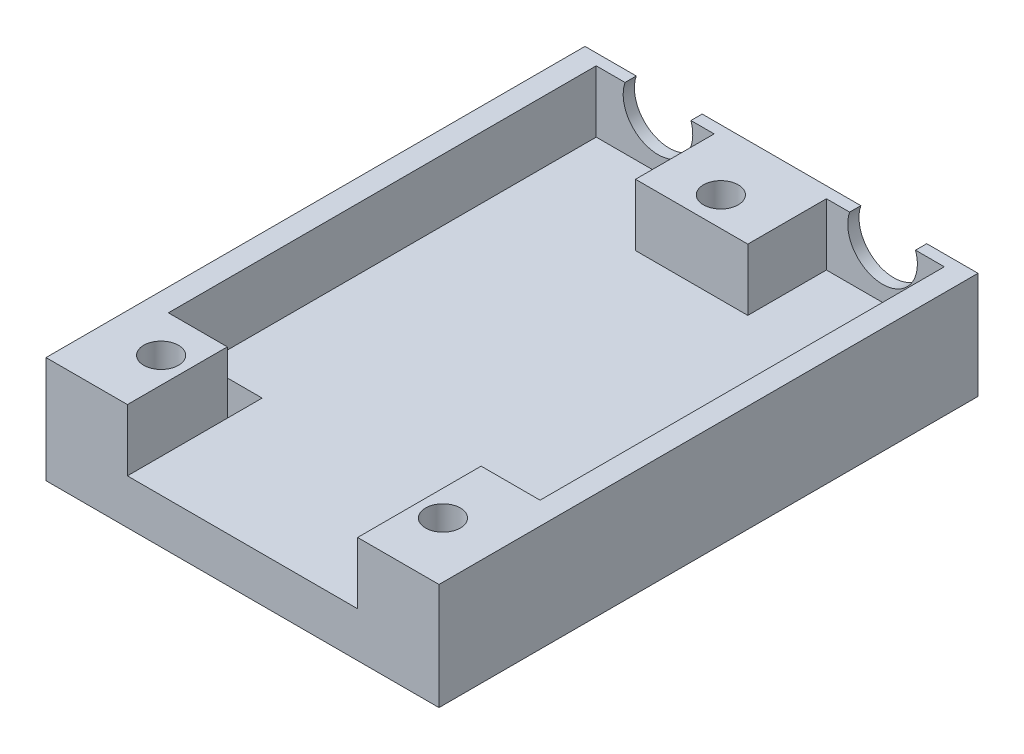
SolidWorks part; units mm, degrees
ref_plane "Front Plane" through (0, 0, 0) normal (0, 0, 1) x (1, 0, 0)
ref_plane "Top Plane" through (0, 0, 0) normal (0, 1, 0) x (1, 0, 0)
ref_plane "Right Plane" through (0, 0, 0) normal (1, 0, 0) x (0, 0, -1)
sketch "Sketch1" plane through (0, 0, 0) normal (0, 1, 0) x (1, 0, 0)
  line L1 (-17.5, 24) -> (17.5, 24)
  line L2 (-17.5, 24) -> (-17.5, -24)
  line L3 (-17.5, -24) -> (17.5, -24)
  line L4 (17.5, 24) -> (17.5, -24)
  line L5 (-44.2539, 0) -> (44.2539, 0) construction
  line L6 (0, -44.7868) -> (0, 44.7868) construction
  dimension "D2" = 35
  dimension "D1" = 48
  dimension "D3" = 24
  dimension "D4" = 17.5
extrude "Boss-Extrude1" add sketch "Sketch1" along normal blind 4
sketch "Sketch2" plane through (0, 4, 0) normal (0, 1, 0) x (1, 0, 0)
  line L1 (-15.5, 23) -> (15.5, 23)
  line L2 (-15.5, 23) -> (-15.5, -21)
  line L3 (-15.5, -21) -> (15.5, -21)
  line L4 (15.5, 23) -> (15.5, -21)
  line L6 (17.5, -24) -> (17.5, 24) construction
  line L7 (-17.5, -24) -> (17.5, -24) construction
  line M5 (-17.5, 24) -> (-17.5, -24)
  line M6 (-17.5, -24) -> (17.5, -24)
  line M7 (17.5, -24) -> (17.5, 24)
  line M8 (17.5, 24) -> (-17.5, 24)
  dimension "D1" = 2
  dimension "D2" = 3
  dimension "D3" = 31
  dimension "D4" = 44
extrude "Boss-Extrude2" add sketch "Sketch2" along normal blind 5.5 contours L1 L4 L3 L2 M8 M5 M6 M7 region at (0, 4, -23.4059)
sketch "Sketch3" plane through (0, 4, 0) normal (0, 1, 0) x (1, 0, 0)
  line L0 (-15.5, 23) -> (15.5, 23) construction
  line L1 (-5, 23) -> (5, 23)
  line L2 (-5, 23) -> (-5, 16)
  line L3 (-5, 16) -> (5, 16)
  line L4 (5, 23) -> (5, 16)
  line L5 (15.5, 23) -> (15.5, -21) construction
  line L7 (-15.5, -21) -> (-10.25, -21)
  line L8 (-15.5, -21) -> (-15.5, -13)
  line L9 (-15.5, -13) -> (-10.25, -13)
  line L10 (-10.25, -21) -> (-10.25, -13)
  line L11 (15.5, -21) -> (10.25, -21)
  line L12 (15.5, -21) -> (15.5, -13)
  line L13 (15.5, -13) -> (10.25, -13)
  line L14 (10.25, -21) -> (10.25, -13)
  dimension "D1" = 10
  dimension "D2" = 7
  dimension "D3" = 10.5
  dimension "D4" = 5.25
  dimension "D5" = 5.25
  dimension "D6" = 8
  dimension "D7" = 8
extrude "Boss-Extrude3" add sketch "Sketch3" along normal blind 5.5
sketch "Sketch4" plane through (0, 0, 24) normal (0, 0, 1) x (1, 0, 0)
  line L0 (-17.5, 9.5) -> (17.5, 9.5) construction
  line L1 (-10.25, 9.5) -> (10.25, 9.5)
  line L2 (-10.25, 9.5) -> (-10.25, 4)
  line L3 (-10.25, 4) -> (10.25, 4)
  line L4 (10.25, 9.5) -> (10.25, 4)
  line L5 (-17.5, 9.5) -> (-17.5, 0) construction
  line L6 (17.5, 9.5) -> (17.5, 0) construction
  dimension "D1" = 7.25
  dimension "D2" = 7.25
  dimension "D3" = 5.5
extrude "Cut-Extrude1" cut sketch "Sketch4" against normal up to surface (3 mm away) up to face at (0, 6.75, 21)
sketch "Sketch5" plane through (0, 0, 0) normal (0, -1, 0) x (1, 0, 0)
  line L0 (44.2539, 0) -> (-44.2539, 0) construction
  line L1 (-2.55, 8.6) -> (2.45, 8.6)
  line L2 (-2.55, 8.6) -> (-2.55, 3.6)
  line L3 (-2.55, 3.6) -> (2.45, 3.6)
  line L4 (2.45, 8.6) -> (2.45, 3.6)
  line L5 (-2.55, -3.6) -> (2.45, -3.6)
  line L6 (-2.55, -3.6) -> (-2.55, -8.6)
  line L7 (-2.55, -8.6) -> (2.45, -8.6)
  line L8 (2.45, -3.6) -> (2.45, -8.6)
  line L9 (17.5, 24) -> (17.5, -24) construction
  dimension "D1" = 5
  dimension "D2" = 7.2
  dimension "D3" = 3.6
  dimension "D4" = 15.05
  dimension "D5" = 15.05
sketch "Sketch6" plane through (0, 0, -24) normal (0, 0, -1) x (-1, 0, 0)
  line L0 (-17.5, 9.5) -> (17.5, 9.5) construction
  line L3 (-17.5, 9.5) -> (-17.5, 0) construction
  arc A0 (-7.0657, 9.5) -> (-12.9343, 9.5) centre (-10, 8.5) cw
  arc A1 (12.9343, 9.5) -> (7.0657, 9.5) centre (10, 8.5) cw
  line M3 (17.5, 9.5) -> (-17.5, 9.5)
  dimension "D1" = 20
  dimension "D3" = 3.1
  dimension "D4" = 3.1
  dimension "D2" = 7.5
  dimension "D5" = 1
  dimension "D6" = 1
extrude "Cut-Extrude2" cut sketch "Sketch6" against normal blind 2 contours A0 M3 | A1 M3 region at (-10, 7.705, -24) region at (10, 7.705, -24)
sketch "Sketch7" plane through (0, 9.5, 0) normal (0, 1, 0) x (1, 0, 0)
  line L1 (-15.5, -12) -> (-10.25, -12)
  line L2 (-15.5, -12) -> (-15.5, -15.1)
  line L3 (-15.5, -15.1) -> (-10.25, -15.1)
  line L4 (-10.25, -12) -> (-10.25, -15.1)
  line L5 (-10.25, -24) -> (-10.25, -13) construction
  line L6 (-17.5, -24) -> (-10.25, -24) construction
  dimension "D1" = 3.1
  dimension "D2" = 5.25
  dimension "D3" = 8.9
extrude "Cut-Extrude3" cut sketch "Sketch7" against normal up to surface (9.5 mm away) up to face at (0, 0, 0)
sketch "Sketch8" plane through (0, 0, 0) normal (0, 1, 0) x (1, 0, 0)
  line L0 (0, -44.7868) -> (0, 44.7868) construction
  line L2 (7.0657, 24) -> (-7.0657, 24) construction
  circle A0 centre (-12.55, -18.7) radius 1.55
  circle A1 centre (12.55, -18.7) radius 1.55
  circle A2 centre (0, 18.6) radius 1.55
  dimension "D1" = 3.1
  dimension "D7" = 3.1
  dimension "D8" = 3.1
  dimension "D2" = 37.3
  dimension "D3" = 25.1
  dimension "D4" = 37.3
  dimension "D5" = 12.55
  dimension "D6" = 5.4
extrude "Cut-Extrude4" cut sketch "Sketch8" along direction (0, 1, 0) on the side against the normal blind 5.5 from surface starting at face at (-14.0461, 9.5, -1.975)
sketch "Sketch9" plane through (0, 0, 0) normal (0, 1, 0) x (1, 0, 0)
  line L0 (-35.1135, -20.6) -> (29.9959, -20.6) construction
  line L1 (-7.0657, 23) -> (-5, 23) construction
  line L2 (-35.1135, 21.9) -> (32.5575, 21.9) construction
  point P4 (-6.0329, 23)
  dimension "D1" = 43.6
  dimension "D2" = 42.5
extrude "Cut-Extrude5" cut sketch "Sketch5" against normal blind 2
equation "\"fWidth\"=35"
equation "\"D2@Sketch1\"=\"fWidth\""
equation "\"fLength\"= 48"
equation "\"D1@Sketch1\"=\"fLength\""
equation "\"D3@Sketch1\"=\"fLength\"/2"
equation "\"D4@Sketch1\"=\"fWidth\"/2"
equation "\"wThickness\"=2"
equation "\"D1@Sketch2\"=\"wThickness\""
equation "\"D3@Sketch2\"=\"fWidth\"- 2* \"wThickness\""
equation "\"D4@Sketch2\"=\"fLength\"- 2 *\"wThickness\""
equation "\"wHeight\"= 5.5"
equation "\"D1@Boss-Extrude2\"=\"wHeight\""
equation "\"D3@Sketch3\"=(\"fWidth\"- 2 *\"wThickness\" - 10)/2"
equation "\"D4@Sketch5\"=(\"fWidth\"- 4.9)/2"
equation "\"D5@Sketch5\"=(\"fWidth\"- 4.9)/2"
equation "\"D3@Sketch4\"=\"wHeight\""
